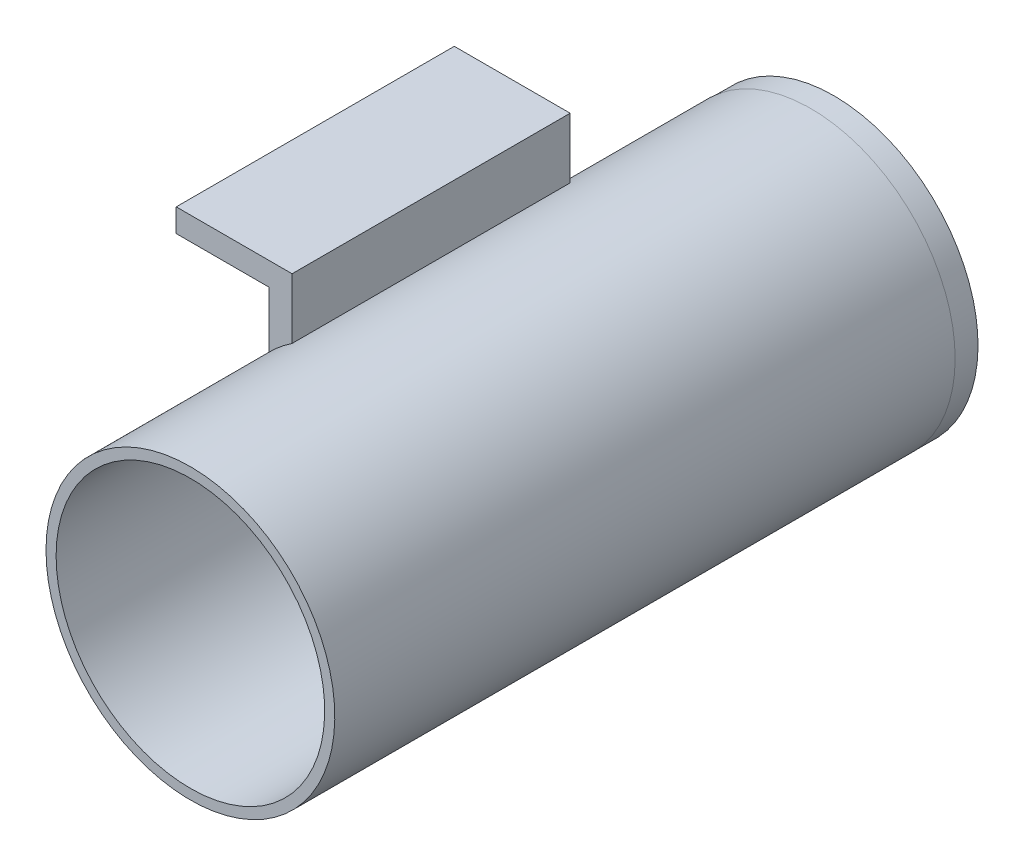
SolidWorks part; units mm, degrees
ref_plane "Front" through (0, 0, 0) normal (0, 0, 1) x (1, 0, 0)
ref_plane "Top" through (0, 0, 0) normal (0, 1, 0) x (1, 0, 0)
ref_plane "Right" through (0, 0, 0) normal (1, 0, 0) x (0, 0, -1)
sketch "Sketch1" plane through (0, 0, 0) normal (0, 0, 1) x (1, 0, 0)
  line L1 (-9.812, 11.8757) -> (-6.637, 11.8757)
  line L2 (-9.812, 11.8757) -> (-9.812, 0.8757)
  line L3 (-9.812, 0.8757) -> (-6.637, 0.8757)
  line L4 (-6.637, 11.8757) -> (-6.637, 0.8757)
  line L5 (-9.812, 8.7007) -> (-22.512, 8.7007)
  line L6 (-9.812, 8.7007) -> (-9.812, 11.8757)
  line L7 (-9.812, 11.8757) -> (-22.512, 11.8757)
  line L8 (-22.512, 8.7007) -> (-22.512, 11.8757)
  dimension "D1" = 11
  dimension "D2" = 3.175
  dimension "D3" = 3.175
  dimension "D4" = 12.7
extrude "Boss-Extrude1" add sketch "Sketch1" along normal blind 38.1 contours L8 L5 L2 L7 | L4 L1 L2 L3 region at (-8.2245, 6.3757, 0) region at (-16.162, 10.2882, 0)
sketch "Sketch2" plane through (0, 0, 0) normal (0, 0, -1) x (-1, 0, 0)
  circle A0 centre (-4.3298, -12.862) radius 19.7846
  circle A1 centre (-4.3298, -12.862) radius 18.4
extrude "Boss-Extrude2" add sketch "Sketch2" against normal blind 63 and the other way blind 22
sketch "Sketch3" plane through (0, 0, -22) normal (0, 0, -1) x (-1, 0, 0)
  circle A0 centre (-4.3256, -12.8973) radius 19.749
extrude "Boss-Extrude3" add sketch "Sketch3" along normal blind 3.175
sketch "Sketch4" plane through (0, 0, -25.175) normal (0, 0, -1) x (-1, 0, 0)
  line L1 (-12.779, -19.0774) -> (-10.2549, -19.0774)
  line L2 (-12.779, -19.0774) -> (-12.779, -29.8463)
  line L3 (-12.779, -29.8463) -> (-10.2549, -29.8463)
  line L4 (-10.2549, -19.0774) -> (-10.2549, -29.8463)
extrude "Cut-Extrude1" cut sketch "Sketch4" against normal blind 3.175
